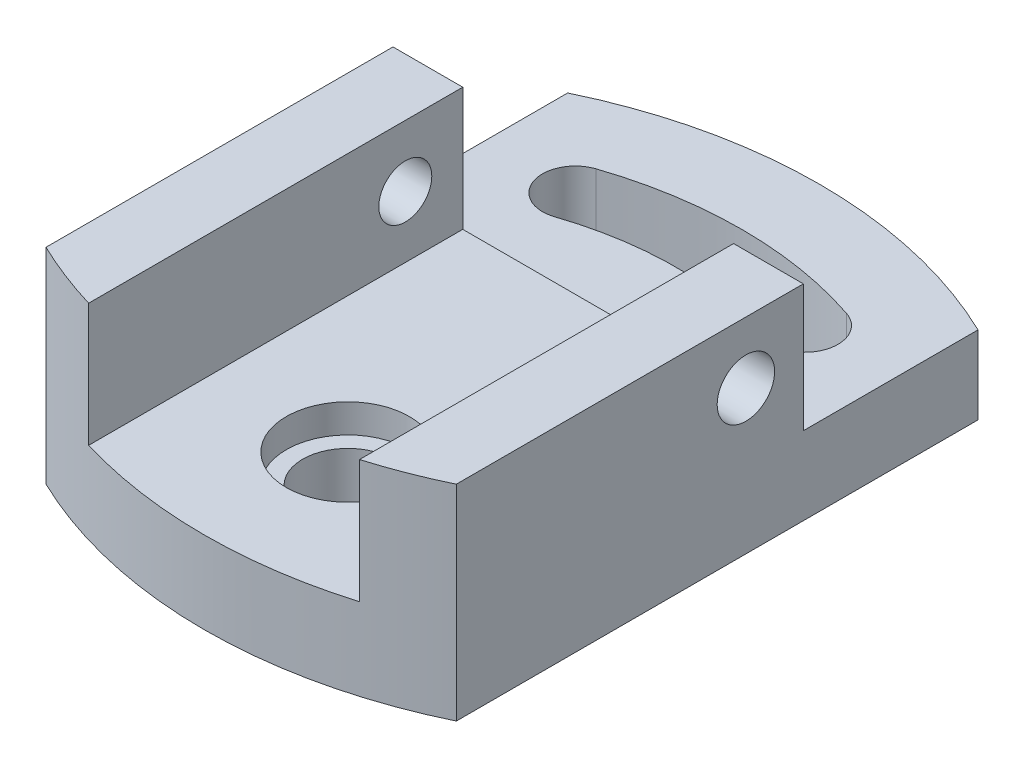
SolidWorks part; units mm, degrees
ref_plane "Front Plane" through (0, 0, 0) normal (0, 0, 1) x (1, 0, 0)
ref_plane "Top Plane" through (0, 0, 0) normal (0, 1, 0) x (1, 0, 0)
ref_plane "Right Plane" through (0, 0, 0) normal (1, 0, 0) x (0, 0, -1)
sketch "Sketch1" plane through (0, 0, 0) normal (0, 1, 0) x (1, 0, 0)
  line L0 (-50, -35) -> (50, -35) construction
  line L1 (-50, 115) -> (50, 115) construction
  line L4 (-50, 103.5616) -> (-50, -23.5616)
  line L5 (50, 103.5616) -> (50, -23.5616)
  line L6 (-33, 61) -> (-50, 61)
  line L7 (-33, 61) -> (33, 61)
  line L8 (-33, 61) -> (-33, -30.1635)
  line L10 (33, 61) -> (33, -30.1635)
  line L11 (33, 61) -> (50, 61)
  circle A2 centre (0, 0) radius 11
  circle A3 centre (0, 0) radius 15
  circle A4 centre (0, 0) radius 88 construction
  arc A5 (-28, 83.4266) -> (28, 83.4266) centre (0, 0) cw construction
  arc A6 (30.5455, 91.0109) -> (-30.5455, 91.0109) centre (0, 0) ccw
  arc A7 (25.4545, 75.8424) -> (-25.4545, 75.8424) centre (0, 0) ccw
  arc A8 (25.4545, 75.8424) -> (30.5455, 91.0109) centre (28, 83.4266) ccw
  arc A9 (-30.5455, 91.0109) -> (-25.4545, 75.8424) centre (-28, 83.4266) ccw
  arc A10 (-50, -23.5616) -> (50, -23.5616) centre (0, 80) ccw
  arc A11 (-50, 103.5616) -> (50, 103.5616) centre (0, 0) cw
  point P8 (0, -35)
  point P15 (0, 88)
  point P20 (0, 61)
  point P25 (0, 115)
  dimension "D1" = 22
  dimension "D2" = 30
  dimension "D3" = 35
  dimension "D6" = 176
  dimension "D7" = 8
  dimension "D8" = 72
  dimension "D10" = 115
  dimension "D11" = 115
  dimension "D4" = 150
  dimension "D5" = 100
  dimension "D9" = 66
  dimension "D12" = 150
  dimension "D13" = 100
  dimension "D14" = 96
extrude "Boss-Extrude1" add sketch "Sketch1" along normal blind 50 contours L4 A10 L8 L6 | L10 A10 L5 L11 region at (-41.394, 0, -16.9186) region at (41.394, 0, -16.9186)
extrude "Boss-Extrude2" add sketch "Sketch1<3>" along normal blind 20 contours L8 A10 L10 L7 A3 region at (0, 0, -15.5527)
sketch "Sketch1<3>" plane through (0, 0, 0) normal (0, 1, 0) x (1, 0, 0) same geometry as "Sketch1"
extrude "Boss-Extrude3" add sketch "Sketch1<4>" along normal blind 19 contours A11 L4 L6 L7 L11 L5 A9 A6 A8 A7 region at (0, 0, -113.8635)
sketch "Sketch1<4>" plane through (0, 0, 0) normal (0, 1, 0) x (1, 0, 0) same geometry as "Sketch1"
extrude "Boss-Extrude4" add sketch "Sketch1<5>" along normal blind 13 contours A3 A2 region at (-14.5757, 0, 0)
sketch "Sketch1<5>" plane through (0, 0, 0) normal (0, 1, 0) x (1, 0, 0) same geometry as "Sketch1"
ref_plane "Plane1" through (0, 35, 0) normal (0, 1, 0) x (1, 0, 0)
sketch "Sketch3" plane through (0, 35, 0) normal (0, 1, 0) x (1, 0, 0)
  line L0 (-50, 47) -> (50.8516, 47) construction
  line L1 (-50, 61) -> (-50, -23.5616) construction
  line L2 (-50, 53.34) -> (50, 54)
  line L3 (50, 61) -> (50, -23.5616) construction
  line L4 (50, 61) -> (-50, 61) construction
  line L5 (-50, 53.34) -> (-50, 47)
  line L6 (50, 54) -> (50, 47)
  line L7 (-50, 47) -> (50, 47)
  dimension "D1" = 14
  dimension "D2" = 14
  dimension "D3" = 12.68
revolve "Cut-Revolve1" cut sketch "Sketch3" angle 360 about L0
